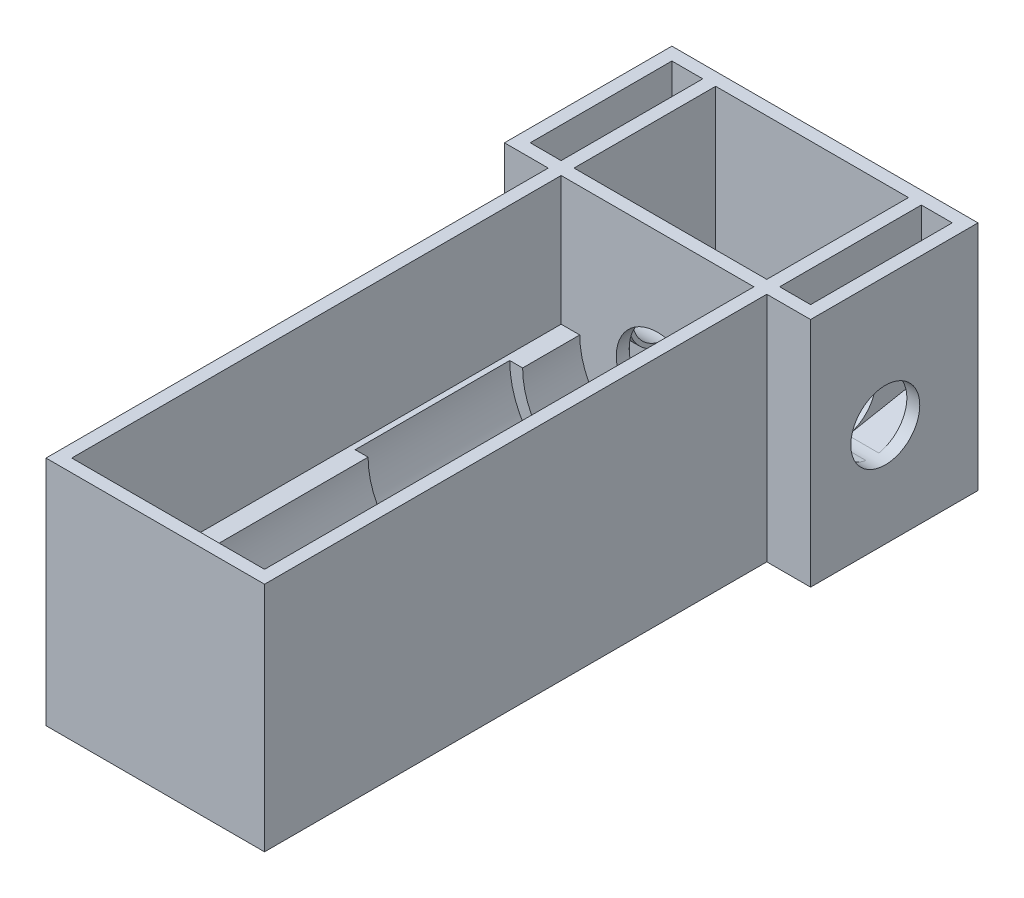
SolidWorks part; units mm, degrees
ref_plane "Front Plane" through (0, 0, 0) normal (0, 0, 1) x (1, 0, 0)
ref_plane "Top Plane" through (0, 0, 0) normal (0, 1, 0) x (1, 0, 0)
ref_plane "Right Plane" through (0, 0, 0) normal (1, 0, 0) x (0, 0, -1)
sketch "Sketch1" plane through (0, 0, 0) normal (0, 0, 1) x (1, 0, 0)
  line L1 (-26.9397, 0) -> (26.9397, 0)
  line L2 (-26.9397, 0) -> (-26.9397, 6.35)
  line L3 (-23.7647, 6.35) -> (23.7647, 6.35)
  line L4 (26.9397, 0) -> (26.9397, 6.35)
  line L6 (-26.9397, 6.35) -> (-26.9397, 57.15)
  line L7 (-26.9397, 57.15) -> (-23.7647, 57.15)
  line L8 (-23.7647, 6.35) -> (-23.7647, 57.15)
  line L10 (26.9397, 6.35) -> (26.9397, 57.15)
  line L11 (26.9397, 57.15) -> (23.7647, 57.15)
  line L12 (23.7647, 6.35) -> (23.7647, 57.15)
  dimension "D1" = 3.175
  dimension "D2" = 53.8795
  dimension "D3" = 6.35
  dimension "D4" = 50.8
extrude "Boss-Extrude1" add sketch "Sketch1" against normal blind 38.1 from offset 15.24
sketch "Sketch2" plane through (0, 0, -22.86) normal (0, 0, 1) x (1, 0, 0)
  line L0 (-26.9397, 0) -> (26.9397, 0) construction
  line L1 (26.9397, 57.15) -> (-26.9397, 57.15)
  line L2 (26.9397, 57.15) -> (26.9397, 0)
  line L3 (26.9397, 0) -> (-26.9397, 0)
  line L4 (-26.9397, 57.15) -> (-26.9397, 0)
extrude "Boss-Extrude2" add sketch "Sketch2" along normal blind 3.175
sketch "Sketch6" plane through (0, 0, 0) normal (0, 0, 1) x (1, 0, 0)
  line L0 (-23.7647, 25.4) -> (-16.1447, 25.4)
  line L3 (-16.1447, 25.4) -> (-16.1447, 34.9)
  line L4 (-16.1447, 34.9) -> (-21.2247, 34.9)
  line L5 (-21.2247, 34.9) -> (-23.7647, 36.068)
  line L6 (0, 25.4) -> (0, 0) construction
  line L7 (-23.7647, 36.068) -> (-23.7647, 25.4)
  line L9 (-23.7647, 6.35) -> (-23.7647, 57.15) construction
  line L10 (23.7647, 36.068) -> (23.7647, 25.4)
  line L11 (21.2247, 34.9) -> (23.7647, 36.068)
  line L12 (16.1447, 34.9) -> (21.2247, 34.9)
  line L13 (16.1447, 25.4) -> (16.1447, 34.9)
  line L15 (23.7647, 25.4) -> (16.1447, 25.4)
  dimension "D1" = 9.5
  dimension "D2" = 5.08
  dimension "D3" = 10.668
  dimension "D4" = 7.62
  dimension "D5" = 25.4
revolve "Revolve2" add sketch "Sketch6" angle 360 about L0
sketch "Sketch3" plane through (0, 0, 0) normal (1, 0, 0) x (0, 0, -1)
  circle A0 centre (0, 25.4) radius 8.5
  circle A1 centre (0, 25.4) radius 9.5 construction
  dimension "D2" = 17
extrude "Cut-Extrude2" cut sketch "Sketch3" against normal through all both and the other way through all
sketch "Sketch7" plane through (0, 0, 0) normal (0, 0, 1) x (1, 0, 0)
  line L0 (23.7647, 6.35) -> (-23.7647, 6.35) construction
  line L1 (-23.7647, 16.2852) -> (-16.1447, 16.2852)
  line L2 (-23.7647, 16.2852) -> (-23.7647, 6.35)
  line L3 (-23.7647, 6.35) -> (-16.1447, 6.35)
  line L4 (-16.1447, 16.2852) -> (-16.1447, 6.35)
  line L5 (-23.7647, 16.2852) -> (-16.1447, 6.35) construction
  line L6 (-23.7647, 6.35) -> (-16.1447, 16.2852) construction
  line L8 (0, 0) -> (0, 25.6446) construction
  line L9 (-26.9397, 0) -> (26.9397, 0) construction
  line L10 (23.7647, 6.35) -> (16.1447, 16.2852) construction
  line L11 (23.7647, 16.2852) -> (16.1447, 6.35) construction
  line L12 (16.1447, 16.2852) -> (16.1447, 6.35)
  line L13 (23.7647, 6.35) -> (16.1447, 6.35)
  line L14 (23.7647, 16.2852) -> (23.7647, 6.35)
  line L15 (23.7647, 16.2852) -> (16.1447, 16.2852)
  line L16 (-23.7647, 6.35) -> (-23.7647, 57.15) construction
  line L17 (-16.1447, 15.9) -> (-16.1447, 34.9) construction
  point P4 (-19.9547, 11.3176)
  point P5 (-16.1447, 16.2852)
  point P18 (19.9547, 11.3176)
extrude "Boss-Extrude7" add sketch "Sketch7" along normal mid plane 3.175
sketch "Sketch8" plane through (0, 0, 15.24) normal (0, 0, -1) x (-1, 0, 0)
  line L1 (26.9397, 57.15) -> (-26.9397, 57.15)
  line L2 (26.9397, 57.15) -> (26.9397, 0)
  line L3 (26.9397, 0) -> (-26.9397, 0)
  line L4 (-26.9397, 57.15) -> (-26.9397, 0)
  line L5 (26.9397, 57.15) -> (-26.9397, 0) construction
  line L6 (26.9397, 0) -> (-26.9397, 57.15) construction
  point P4 (0, 28.575)
extrude "Boss-Extrude8" add sketch "Sketch8" against normal blind 127
sketch "Sketch9" plane through (0, 0, 0) normal (1, 0, 0) x (0, 0, -1)
  line L0 (0, 25.4) -> (-142.24, 25.4) construction
  line L1 (-142.24, 0) -> (-142.24, 57.15) construction
  line L2 (-70.6, 47.752) -> (-70.6, 44.577)
  line L3 (-70.6, 47.752) -> (-32.5, 47.752)
  line L4 (-32.5, 47.752) -> (-32.5, 44.577)
  line L5 (-32.5, 44.577) -> (-20.1041, 44.577)
  line L6 (0, 35.56) -> (0, 25.4)
  line L7 (0, 25.4) -> (22.86, 25.4) construction
  line L8 (22.86, 6.35) -> (22.86, 57.15) construction
  line L9 (0, 25.4) -> (-70.104, 25.4)
  line L10 (-70.6, 44.577) -> (-139.065, 44.577)
  line L11 (-139.065, 44.577) -> (-139.065, 25.4)
  line L12 (-139.065, 25.4) -> (-70.104, 25.4)
  line L13 (-20.1041, 44.577) -> (-20.1041, 35.56)
  line L14 (-20.1041, 35.56) -> (0, 35.56)
  dimension "D1" = 38.1
  dimension "D2" = 10.16
  dimension "D3" = 22.352
  dimension "D4" = 3.175
  dimension "D5" = 3.175
  dimension "D6" = 32.5
revolve "Cut-Revolve1" cut sketch "Sketch9" angle 360 about L9
ref_axis "Axis2" through (0, 25.4, 70.6) along (0, 0, -1)
ref_axis "Axis3" through (-26.9397, 25.4, 0) along (1, 0, 0)
ref_plane "Plane2" through (0, 25.4, 0) normal (0, -1, 0) x (-1, 0, 0)
sketch "Sketch13" plane through (0, 0, 0) normal (0, -1, 0) x (-1, 0, 0)
  line L0 (26.9397, -142.24) -> (26.9397, 22.86) construction
  line L1 (26.9397, -15.4709) -> (26.9421, -15.4709)
  line L2 (26.9397, -15.4709) -> (26.9397, -142.24)
  line L3 (26.9397, -142.24) -> (26.9421, -142.24)
  line L4 (26.9421, -15.4709) -> (26.9421, -142.24)
  line L5 (26.9397, -15.4709) -> (26.9421, -142.24) construction
  line L6 (26.9397, -142.24) -> (26.9421, -15.4709) construction
  line L7 (26.9397, -142.24) -> (-26.9397, -142.24) construction
  line L9 (-26.9397, -142.24) -> (-26.9374, -142.24)
  line L10 (-26.9397, -142.24) -> (-26.9397, -15.4709)
  line L11 (-26.9397, -15.4709) -> (-26.9374, -15.4709)
  line L12 (-26.9374, -142.24) -> (-26.9374, -15.4709)
  line L13 (-26.9397, -142.24) -> (-26.9374, -15.4709) construction
  line L14 (-26.9397, -15.4709) -> (-26.9374, -142.24) construction
  point P4 (26.9409, -78.8555)
  point P13 (-26.9386, -78.8555)
extrude "Cut-Extrude7" cut sketch "Sketch13" against normal through all both and the other way through all
sketch "Sketch14" plane through (0, 57.15, 0) normal (0, 1, 0) x (1, 0, 0)
  line L1 (23.7624, -139.065) -> (-23.7647, -139.065)
  line L2 (23.7624, -139.065) -> (23.7624, -18.415)
  line L3 (23.7624, -18.415) -> (-23.7647, -18.415)
  line L4 (-23.7647, -139.065) -> (-23.7647, -18.415)
  line L5 (23.7624, -139.065) -> (-23.7647, -18.415) construction
  line L6 (23.7624, -18.415) -> (-23.7647, -139.065) construction
  line L7 (26.9374, -142.24) -> (-26.9397, -142.24) construction
  line L8 (26.9374, -142.24) -> (26.9374, -15.4709) construction
  line L10 (23.7647, -15.24) -> (-23.7647, -15.24) construction
  line L11 (-26.9397, -142.24) -> (-26.9397, 22.86) construction
  point P4 (-0.0012, -78.74)
  dimension "D1" = 3.175
  dimension "D2" = 3.175
  dimension "D3" = 3.175
  dimension "D4" = 3.175
extrude "Cut-Extrude8" cut sketch "Sketch14" against normal up to surface (31.75 mm away) up to plane "Plane2"
sketch "Sketch15" plane through (0, 0, 20.1041) normal (0, 0, 1) x (1, 0, 0)
  line L1 (-10.16, 25.4) -> (-19.177, 25.4)
  line L2 (-10.16, 25.4) -> (-19.177, 25.4)
  line L4 (19.177, 25.4) -> (10.16, 25.4)
  line L5 (19.177, 25.4) -> (10.16, 25.4)
  arc A2 (-19.177, 25.4) -> (19.177, 25.4) centre (0, 25.4) ccw
  arc A3 (-10.16, 25.4) -> (10.16, 25.4) centre (0, 25.4) ccw
  arc A4 (-19.177, 25.4) -> (19.177, 25.4) centre (0, 25.4) ccw
  arc A5 (-10.16, 25.4) -> (10.16, 25.4) centre (0, 25.4) ccw
  dimension "D1" = 0
extrude "Cut-Extrude9" cut sketch "Sketch15" against normal up to surface (1.6891 mm away) up to face at (-0.0008, 37.6767, 18.415)
sketch "Sketch18" plane through (0, 0, 0) normal (0, 1, 0) x (1, 0, 0)
  line L1 (-23.7647, 22.86) -> (-37.7347, 22.86)
  line L2 (-23.7647, 22.86) -> (-23.7647, -18.415)
  line L3 (-23.7647, -18.415) -> (-37.7347, -18.415)
  line L4 (-37.7347, 22.86) -> (-37.7347, -18.415)
  line L5 (-23.7647, 22.86) -> (-37.7347, -18.415) construction
  line L6 (-23.7647, -18.415) -> (-37.7347, 22.86) construction
  line L7 (-23.7647, -15.24) -> (-23.7647, 19.685) construction
  line L8 (-19.177, -18.415) -> (-23.7647, -18.415) construction
  line L9 (-26.9397, -142.24) -> (-26.9397, 22.86) construction
  line L10 (-34.5597, 19.685) -> (-26.9397, 19.685)
  line L11 (-34.5597, 19.685) -> (-34.5597, -15.24)
  line L12 (-34.5597, -15.24) -> (-26.9397, -15.24)
  line L13 (-26.9397, 19.685) -> (-26.9397, -15.24)
  line L14 (-34.5597, 19.685) -> (-26.9397, -15.24) construction
  line L15 (-34.5597, -15.24) -> (-26.9397, 19.685) construction
  line L16 (26.9397, 22.86) -> (-26.9397, 22.86) construction
  point P4 (-30.7497, 2.2225)
  point P15 (-30.7497, 2.2225)
  dimension "D1" = 7.62
  dimension "D2" = 3.175
  dimension "D3" = 3.175
extrude "Boss-Extrude10" add sketch "Sketch18" along normal up to surface (57.15 mm away) up to face at (-0.0012, 57.15, 78.74)
sketch "Sketch19" plane through (-26.9397, 0, 0) normal (1, 0, 0) x (0, 0, -1)
  line L0 (1.5875, 17.0496) -> (22.225, 20.973)
  line L2 (-1.5875, 17.0496) -> (-15.24, 19.645)
  line L3 (-15.24, 15.24) -> (-15.24, 35.56) construction
  line L4 (-15.24, 19.645) -> (-15.24, 0)
  line L5 (-15.24, 0) -> (22.225, 0)
  line L6 (22.225, 0) -> (22.225, 20.973)
  arc A0 (-1.5875, 17.0496) -> (1.5875, 17.0496) centre (0, 25.4) ccw
  circle A1 centre (0, 25.4) radius 8.5 construction
  point P1 (0, 0)
  point P5 (19.05, 0)
  point P6 (0, 0)
  point P12 (22.225, 0)
  dimension "D1" = 3.175
extrude "Boss-Extrude11" add sketch "Sketch19" against normal up to next
mirror "Mirror4" about plane through (0, 0, 0) normal (1, 0, 0) of "Boss-Extrude11", "Boss-Extrude10"
sketch "Sketch20" plane through (-23.7647, 0, 0) normal (1, 0, 0) x (0, 0, -1)
  circle A0 centre (0, 25.4) radius 8.5 construction
  circle A1 centre (0, 25.4) radius 8.5
extrude "Cut-Extrude11" cut sketch "Sketch20" against normal through all both and the other way through all
ref_axis "Axis4" through (0, 25.4, 18.415) along (0, 0, -1)
